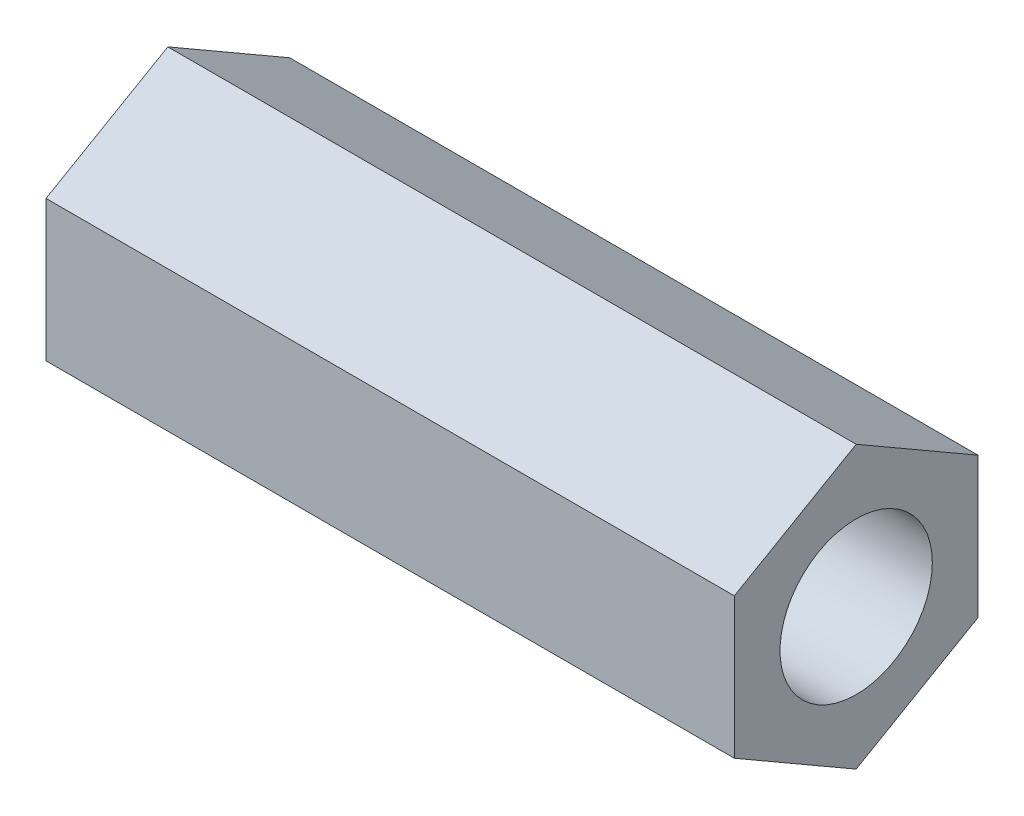
SolidWorks part; units mm, degrees
ref_plane "Front Plane" through (0, 0, 0) normal (0, 0, 1) x (1, 0, 0)
ref_plane "Top Plane" through (0, 0, 0) normal (0, 1, 0) x (1, 0, 0)
ref_plane "Right Plane" through (0, 0, 0) normal (1, 0, 0) x (0, 0, -1)
sketch "Sketch1" plane through (0, 0, 0) normal (1, 0, 0) x (0, 0, -1)
  line L1 (0, 4.6188) -> (-4, 2.3094)
  line L2 (-4, 2.3094) -> (-4, -2.3094)
  line L3 (-4, -2.3094) -> (0, -4.6188)
  line L4 (0, -4.6188) -> (4, -2.3094)
  line L5 (4, -2.3094) -> (4, 2.3094)
  line L6 (4, 2.3094) -> (0, 4.6188)
  circle A0 centre (0, 0) radius 4 construction
  circle A1 centre (0, 0) radius 2.5
extrude "Boss-Extrude1" add sketch "Sketch1" along normal blind 22.6
